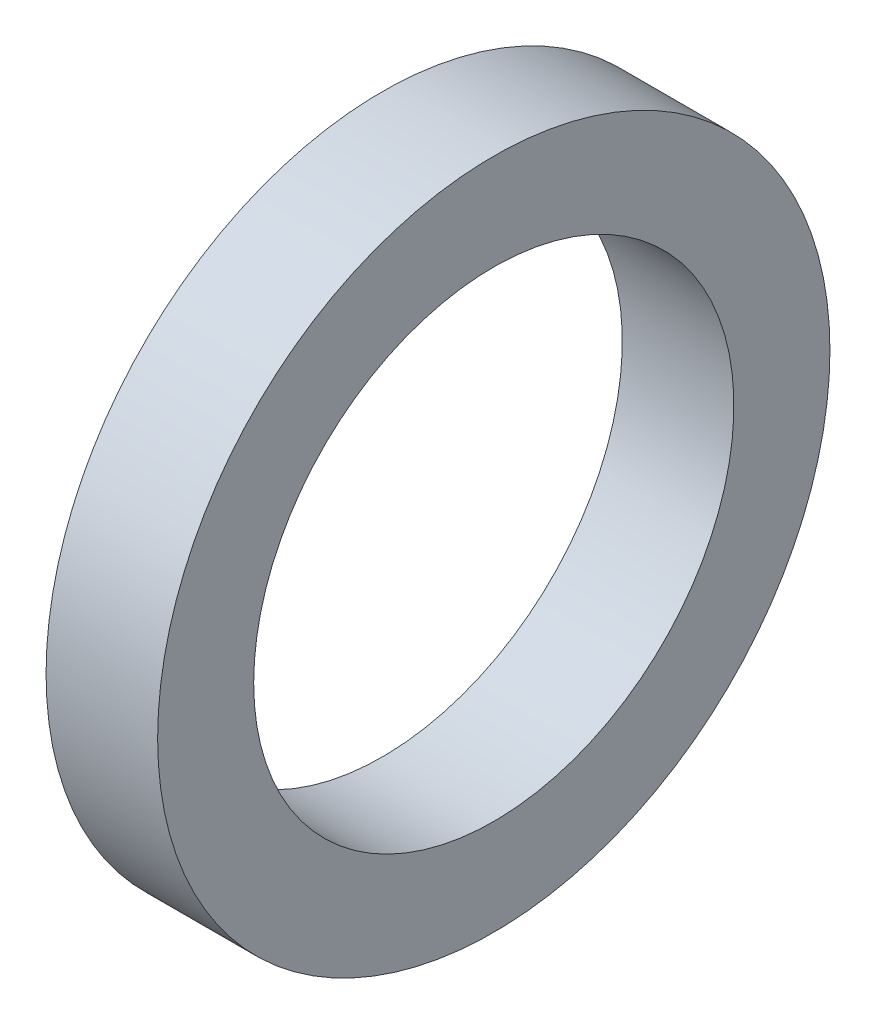
SolidWorks part; units mm, degrees
ref_plane "Front Plane" through (0, 0, 0) normal (0, 0, 1) x (1, 0, 0)
ref_plane "Top Plane" through (0, 0, 0) normal (0, 1, 0) x (1, 0, 0)
ref_plane "Right Plane" through (0, 0, 0) normal (1, 0, 0) x (0, 0, -1)
sketch "Sketch2" plane through (0, 0, 0) normal (0, 0, 1) x (1, 0, 0)
  line L0 (0, 0) -> (58.591, 0) construction
  line L2 (0, 0) -> (18.4, 0)
  line L3 (0, 0) -> (0, 2.5)
  line L4 (0, 2.5) -> (18.4, 2.5)
  line L5 (18.4, 0) -> (18.4, 2.5)
  line L6 (6.0094, 2.5) -> (6.0094, 6)
  line L11 (6.0094, 6) -> (9.9794, 6)
  line L16 (12.9794, 6) -> (12.9794, 3)
  line L17 (12.9794, 3) -> (13.6398, 3)
  line L18 (13.6398, 3) -> (13.6398, 2.5)
  line L19 (13.6398, 2.5) -> (6.0094, 2.5)
  line L22 (13.6398, 2.5) -> (16.1198, 2.5)
  line L23 (13.6398, 2.5) -> (13.6398, 4)
  line L24 (13.6398, 4) -> (16.1198, 4)
  line L25 (16.1198, 2.5) -> (16.1198, 4)
  line L27 (6.0094, 6) -> (9.9794, 6)
  line L28 (6.0094, 6) -> (6.0094, 9)
  line L29 (6.0094, 9) -> (9.9794, 9)
  line L30 (9.9794, 6) -> (9.9794, 9)
  line L31 (6.0094, 9) -> (6.0094, 8.25)
  line L32 (6.0094, 8.25) -> (5.0094, 8.25)
  line L33 (8.6609, 22.001) -> (8.6609, 12.476) construction
  line L34 (5.0094, 12.476) -> (12.3124, 12.476)
  line L35 (9.9794, 9) -> (12.3124, 9)
  line L36 (5.0094, 7.9375) -> (1.8344, 7.9375)
  line L37 (5.0094, 8.25) -> (5.0094, 12.476)
  line L38 (5.0094, 7.9375) -> (5.0094, 13.9365)
  line L39 (5.0094, 13.9365) -> (1.8344, 13.9365)
  line L40 (1.8344, 7.9375) -> (1.8344, 13.9365)
  line L41 (5.0094, 22.001) -> (12.3124, 22.001)
  line L42 (5.0094, 22.001) -> (5.0094, 30.1625)
  line L43 (5.0094, 30.1625) -> (12.3124, 30.1625)
  line L44 (12.3124, 22.001) -> (12.3124, 30.1625)
  line L49 (16.6398, 22.001) -> (16.6398, 7.5)
  line L51 (23.0198, 7.5) -> (23.0198, 6.5)
  line L54 (16.1198, 4) -> (13.6398, 4)
  line L56 (18.0398, 7.5) -> (23.0198, 7.5)
  line L57 (13.3124, 22.001) -> (16.6398, 22.001)
  line L58 (16.1198, 3.5) -> (20.0198, 3.5)
  line L59 (29.9098, 14) -> (26.9098, 11)
  line L60 (4.0094, 31.75) -> (18.0398, 31.75)
  line L61 (18.0398, 7.5) -> (23.0198, 7.5)
  line L62 (18.0398, 7.5) -> (18.0398, 12)
  line L63 (18.0398, 12) -> (23.0198, 12)
  line L64 (23.0198, 7.5) -> (23.0198, 12)
  line L65 (18.0398, 31.75) -> (18.0398, 12)
  line L66 (23.0198, 11) -> (26.9098, 11)
  line L67 (34.8098, 23) -> (31.3098, 19.5)
  line L68 (35.8098, 31) -> (38.7998, 33.99)
  line L69 (29.9098, 14) -> (29.9098, 15)
  line L70 (29.9098, 15) -> (22.9398, 15)
  line L71 (22.9398, 15) -> (21.0398, 15)
  line L72 (18.0398, 7.5) -> (16.6398, 7.5)
  line L73 (21.0398, 15) -> (21.0398, 43)
  line L74 (19.5798, 40) -> (9.6198, 40)
  line L75 (9.6198, 40) -> (4.0094, 40)
  line L76 (21.0398, 43) -> (19.5798, 43)
  line L77 (22.9398, 15) -> (29.9098, 15)
  line L78 (22.9398, 15) -> (22.9398, 21)
  line L79 (22.9398, 21) -> (29.9098, 21)
  line L80 (29.9098, 15) -> (29.9098, 21)
  line L81 (9.6198, 40) -> (19.5798, 40)
  line L82 (9.6198, 40) -> (9.6198, 50)
  line L83 (9.6198, 50) -> (19.5798, 50)
  line L84 (19.5798, 40) -> (19.5798, 50)
  line L85 (4.0094, 40) -> (4.0094, 31.75)
  line L86 (12.9794, 3) -> (12.9794, 2.5)
  line L87 (31.3098, 19.5) -> (29.9098, 19.5)
  line L88 (21.4694, 63.5) -> (21.4694, 51.308)
  line L89 (21.4694, 63.5) -> (25.9398, 63.5)
  line L90 (25.9398, 63.5) -> (25.9398, 25)
  line L91 (27.8398, 25) -> (25.9398, 25)
  line L92 (9.6198, 48) -> (8.1598, 48)
  line L93 (8.1598, 48) -> (8.1598, 53.476)
  line L94 (8.1598, 53.476) -> (19.5798, 53.476)
  line L95 (19.5798, 53.476) -> (19.5798, 50)
  line L96 (13.8698, 63.001) -> (13.8698, 53.476) construction
  line L97 (8.1598, 63.001) -> (19.5798, 63.001)
  line L98 (8.1598, 63.001) -> (8.1598, 68.2625)
  line L99 (8.1598, 68.2625) -> (19.5798, 68.2625)
  line L100 (19.5798, 63.001) -> (19.5798, 68.2625)
  line L101 (12.9794, 6) -> (11.9794, 6)
  line L102 (8.1598, 44.825) -> (4.9848, 44.825)
  line L103 (8.1598, 44.825) -> (8.1598, 54.9365)
  line L104 (8.1598, 54.9365) -> (4.9848, 54.9365)
  line L106 (9.9794, 6) -> (10.8794, 6)
  line L107 (27.8398, 25) -> (34.8098, 25)
  line L108 (34.8098, 25) -> (34.8098, 23)
  line L109 (0, 0) -> (-2, 0)
  line L110 (0, 0) -> (0, 11)
  line L111 (27.8398, 25) -> (34.8098, 25)
  line L112 (27.8398, 25) -> (27.8398, 32.5)
  line L113 (27.8398, 32.5) -> (34.8098, 32.5)
  line L114 (34.8098, 25) -> (34.8098, 32.5)
  line L115 (35.8098, 31) -> (34.8098, 31)
  line L116 (27.8398, 32.5) -> (27.8398, 64.5)
  line L117 (20.5373, 74.025) -> (6.2023, 74.025)
  line L118 (6.2023, 74.025) -> (6.2023, 76.2)
  line L119 (38.7998, 47.29) -> (30.8398, 55.25)
  line L120 (0, 11) -> (-2, 11)
  line L121 (38.7998, 43.815) -> (30.8623, 43.815)
  line L123 (-4.8152, 69.85) -> (1.5348, 76.2)
  line L124 (38.7998, 47.29) -> (38.7998, 33.99)
  line L125 (-2, 0) -> (-2, 11)
  line L126 (38.7998, 37.465) -> (30.8623, 37.465)
  line L127 (30.8623, 43.815) -> (30.8623, 37.465)
  line L128 (6.0094, 2.5) -> (6.0094, 0)
  line L129 (-0.0152, 63.5) -> (-0.0152, 30)
  line L132 (4.9848, 63.5) -> (-0.0152, 63.5)
  line L136 (-1.8152, 30) -> (-11.7752, 30)
  line L138 (-13.7752, 25.4) -> (-2, 25.4)
  line L139 (-2, 25.4) -> (-2, 11.5)
  line L140 (27.8398, 64.5) -> (20.5373, 64.5)
  line L141 (-1.8152, 30) -> (-11.7752, 30)
  line L142 (-1.8152, 30) -> (-1.8152, 39)
  line L143 (-1.8152, 39) -> (-11.7752, 39)
  line L144 (-11.7752, 30) -> (-11.7752, 39)
  line L145 (20.5373, 64.5) -> (20.5373, 74.025)
  line L146 (-12.7752, 37) -> (-12.7752, 47.29)
  line L147 (-12.7752, 37) -> (-11.7752, 37)
  line L148 (30.8398, 55.25) -> (30.8398, 76.2)
  line L149 (11.9794, 6) -> (11.9794, 5.45)
  line L154 (-2, 11.5) -> (0.5, 11.5)
  line L155 (4.9848, 60.6197) -> (24.0348, 60.6197)
  line L160 (4.9848, 60.6197) -> (4.9848, 55.8572)
  line L161 (4.9848, 55.8572) -> (24.0348, 55.8572)
  line L166 (24.0348, 60.6197) -> (24.0348, 55.8572)
  line L167 (4.9848, 60.6197) -> (24.0348, 55.8572) construction
  line L172 (4.9848, 55.8572) -> (24.0348, 60.6197) construction
  line L173 (24.0348, 62.2072) -> (25.9398, 62.2072)
  line L174 (11.9794, 5.45) -> (10.8794, 5.45)
  line L175 (10.8794, 6) -> (10.8794, 5.45)
  line L176 (24.0348, 62.2072) -> (24.0348, 54.2697)
  line L177 (24.0348, 54.2697) -> (25.9398, 54.2697)
  line L178 (25.9398, 62.2072) -> (25.9398, 54.2697)
  line L179 (24.0348, 62.2072) -> (25.9398, 54.2697) construction
  line L180 (24.0348, 54.2697) -> (25.9398, 62.2072) construction
  line L181 (3, 19.6197) -> (15.7, 19.6197)
  line L182 (3, 19.6197) -> (3, 14.8572)
  line L183 (3, 14.8572) -> (15.7, 14.8572)
  line L184 (15.7, 19.6197) -> (15.7, 14.8572)
  line L185 (3, 19.6197) -> (15.7, 14.8572) construction
  line L186 (3, 14.8572) -> (15.7, 19.6197) construction
  line L187 (15.7, 21.2072) -> (16.6398, 21.2072)
  line L188 (15.7, 21.2072) -> (15.7, 13.2697)
  line L189 (15.7, 13.2697) -> (16.6398, 13.2697)
  line L190 (16.6398, 21.2072) -> (16.6398, 13.2697)
  line L191 (15.7, 21.2072) -> (16.6398, 13.2697) construction
  line L192 (15.7, 13.2697) -> (16.6398, 21.2072) construction
  line L193 (0.5, 11.5) -> (0.5, 6.9375)
  line L194 (0.5, 6.9375) -> (1.8344, 6.9375)
  line L195 (23.0198, 6.5) -> (20.0198, 3.5)
  line L196 (4.9848, 63.5) -> (4.9848, 54.9365)
  line L197 (3, 43.825) -> (4.9848, 43.825)
  line L198 (1.8344, 6.9375) -> (1.8344, 7.9375)
  line L199 (6.0094, 0) -> (12.9794, 0)
  line L200 (12.9794, 0) -> (12.9794, 2.5)
  line L201 (18.0398, 31.75) -> (18.0398, 35.875)
  line L202 (18.0398, 35.875) -> (21.0398, 35.875)
  line L203 (30.8398, 76.2) -> (6.2023, 76.2)
  line L204 (2.7573, 69.85) -> (7.2023, 69.85) construction
  line L205 (7.2023, 67.4688) -> (26.2523, 67.4688)
  line L206 (7.2023, 74.025) -> (7.2023, 64.5)
  line L207 (7.2023, 64.5) -> (-1.8152, 64.5)
  line L208 (-1.8152, 64.5) -> (-1.8152, 39)
  line L209 (-12.7752, 47.29) -> (-4.8152, 55.25)
  line L210 (-4.8152, 55.25) -> (-4.8152, 69.85)
  line L211 (7.2023, 67.4688) -> (7.2023, 72.2312)
  line L212 (7.2023, 72.2312) -> (26.2523, 72.2313)
  line L213 (26.2523, 67.4688) -> (26.2523, 72.2313)
  line L214 (26.2523, 73.8187) -> (30.8398, 73.8187)
  line L215 (26.2523, 73.8187) -> (26.2523, 65.8813)
  line L216 (26.2523, 65.8813) -> (30.8398, 65.8813)
  line L217 (30.8398, 73.8187) -> (30.8398, 65.8813)
  line L218 (2.7573, 72.2313) -> (24.9823, 72.2313)
  line L219 (2.7573, 72.2313) -> (2.7573, 67.4687)
  line L220 (2.7573, 67.4687) -> (24.9823, 67.4687)
  line L221 (24.9823, 72.2313) -> (24.9823, 67.4687)
  line L222 (24.9823, 69.85) -> (20.5373, 69.85) construction
  line L223 (21.4694, 51.308) -> (22.9398, 51.308)
  line L224 (22.9398, 51.308) -> (22.9398, 21)
  line L225 (13.6398, 4) -> (13.6398, 12.2697)
  line L226 (13.6398, 12.2697) -> (13.3124, 12.2697)
  line L227 (13.3124, 12.2697) -> (13.3124, 22.001)
  line L228 (12.3124, 9) -> (12.3124, 12.476)
  line L229 (-1.8152, 30) -> (-0.0152, 30)
  line L230 (8.1598, 65.6317) -> (2.7573, 65.6317) construction
  line L231 (19.5798, 65.6317) -> (24.9823, 65.6317) construction
  line L232 (1.5348, 76.2) -> (6.2023, 76.2)
  line L233 (-11.7752, 30) -> (-13.7752, 30)
  line L234 (-13.7752, 30) -> (-13.7752, 25.4)
  line L235 (3, 13.9365) -> (3, 43.825)
  line L236 (4.9848, 54.9365) -> (4.9848, 44.825)
  line L237 (4.9848, 43.825) -> (4.9848, 44.825)
  circle A0 centre (26.8898, 25.95) radius 0.95
  circle A1 centre (21.9898, 15.95) radius 0.95
  circle A2 centre (17.3398, 8.2) radius 0.7
  circle A3 centre (10.4294, 6.45) radius 0.45
  circle A4 centre (-0.9152, 30.9) radius 0.9
  point P7 (24.9873, 58.2385)
  point P131 (16.1699, 17.2385)
  point P135 (14.5098, 58.2385)
  point P146 (9.35, 17.2385)
sketch "Sketch3" plane through (0, 0, 0) normal (0, 0, 1) x (1, 0, 0)
  line L0 (22.9398, 21) -> (29.9098, 21) construction
  line L1 (29.9098, 15) -> (29.9098, 21) construction
  line L2 (29.9098, 15) -> (22.9398, 15) construction
  line L3 (22.9398, 15) -> (22.9398, 21) construction
  line L4 (22.9398, 21) -> (29.9098, 21)
  line L5 (29.9098, 15) -> (29.9098, 21)
  line L6 (29.9098, 15) -> (22.9398, 15)
  line L7 (22.9398, 15) -> (22.9398, 21)
revolve "Revolve1" add sketch "Sketch3" angle 360 about L0
